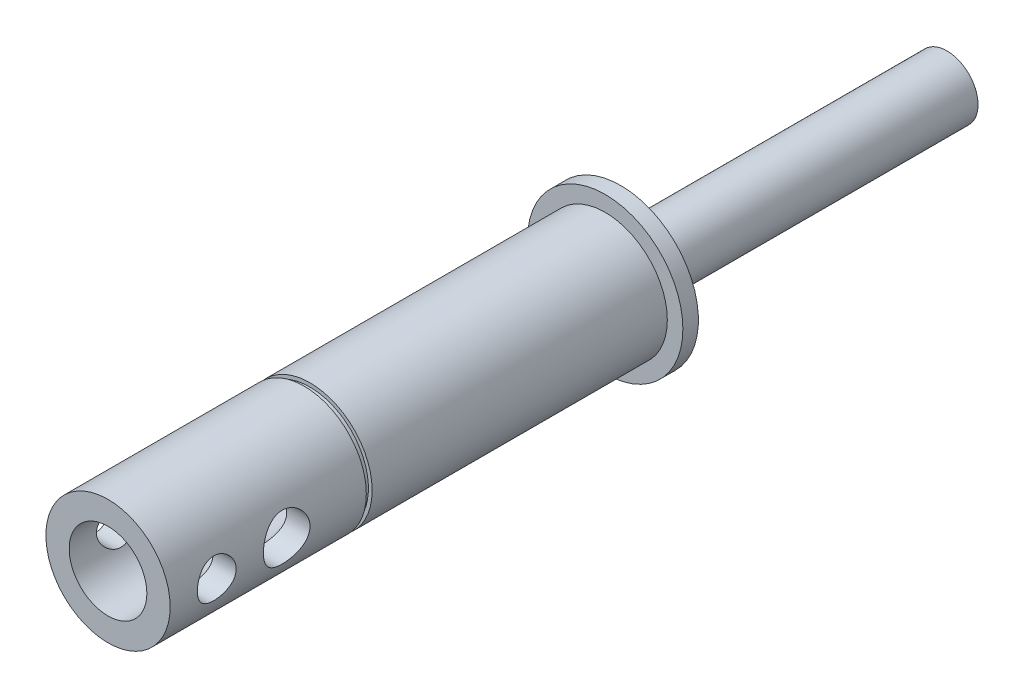
SolidWorks part; units mm, degrees
other "Markup1"
sketch "Sketch20" plane through (-15.875, -15.875, 171.45) normal (-1, 0, 0) x (0, 0, -1)
material "6061 Alloy"
ref_plane "Front Plane" through (0, 0, 0) normal (0, 0, 1) x (1, 0, 0)
ref_plane "Top Plane" through (0, 0, 0) normal (0, 1, 0) x (1, 0, 0)
ref_plane "Right Plane" through (0, 0, 0) normal (1, 0, 0) x (0, 0, -1)
sketch "Sketch1" plane through (0, 0, 0) normal (0, 0, 1) x (1, 0, 0)
  circle A0 centre (0, 0) radius 15.875
  dimension "D1" = 31.75
extrude "RawStock" add sketch "Sketch1" along normal blind 194.6402
sketch "Sketch10" plane through (0, 0, 194.6402) normal (0, 0, 1) x (1, 0, 0)
  circle A0 centre (0, 0) radius 12.7
extrude "FacingOp" cut sketch "Sketch10" against normal blind 23.1902
hole_wizard "ReliefHole" positions "Sketch2" profile "Sketch3" legacy
sketch "Sketch2" plane through (0, 0, 194.6402) normal (0, 0, 1) x (1, 0, 0)
  point P0 (0, 0)
sketch "Sketch3" plane through (0, 0, 194.6402) normal (1, 0, 0) x (0, -1, 0)
  line L0 (0, 0) -> (0, 95.8905)
  line L1 (0, 95.8905) -> (6.35, 92.075)
  line L2 (6.35, 92.075) -> (6.35, 0)
  line L4 (6.35, 0) -> (0, 0)
  line L6 (0, 95.8905) -> (-6.35, 92.075) construction
  line L7 (0, -4.2442) -> (0, 117.3081) construction
  dimension "Diameter" = 12.7
  dimension "Depth" = 92.075
  dimension "Drill Angle" = 118
hole_wizard "WiresHole" positions "Sketch4" profile "Sketch5" legacy
sketch "Sketch4" plane through (0, 0, 194.6402) normal (0, 0, 1) x (1, 0, 0)
  point P0 (0, 0)
sketch "Sketch5" plane through (0, 0, 194.6402) normal (1, 0, 0) x (0, -1, 0)
  line L0 (0, 0) -> (0, 120.0345)
  line L1 (0, 120.0345) -> (7.9375, 115.2652)
  line L2 (7.9375, 115.2652) -> (7.9375, 0)
  line L4 (7.9375, 0) -> (0, 0)
  line L6 (0, 120.0345) -> (-7.9375, 115.2652) construction
  line L7 (0, -4.2442) -> (0, 117.3081) construction
  dimension "Diameter" = 15.875
  dimension "Depth" = 115.2652
  dimension "Drill Angle" = 118
sketch "Sketch6" plane through (0, 0, 194.6402) normal (0, 0, 1) x (1, 0, 0)
  circle A0 centre (0, 0) radius 12.7
  dimension "D1" = 25.4
extrude "ShaftDiam" cut sketch "Sketch6" against normal blind 124.7902 flip side to cut
ref_plane "GroovePlane" through (0, 0, 130.175) normal (0, 0, 1) x (1, 0, 0)
sketch "Sketch7" plane through (0, 0, 130.175) normal (0, 0, 1) x (1, 0, 0)
  circle A0 centre (0, 0) radius 11.938
  dimension "D1" = 23.876
extrude "Groove" cut sketch "Sketch7" along normal blind 1.1906 flip side to cut
sketch "Sketch8" plane through (0, 0, 0) normal (0, 0, -1) x (-1, 0, 0)
  circle A0 centre (0, 0) radius 6.35
  dimension "D1" = 12.7
extrude "EncoderShaft" cut sketch "Sketch8" against normal blind 66.675 flip side to cut
sketch "Sketch9" plane through (0, 0, 0) normal (0, 0, -1) x (-1, 0, 0)
  circle A0 centre (0, 0) radius 6.35
  dimension "D1" = 12.7
ref_plane "Plane2" through (-12.7, 0, 0) normal (-1, 0, 0) x (0, 1, 0)
sketch "Sketch12" plane through (-12.7, 0, 0) normal (-1, 0, 0) x (0, 1, 0)
  line L0 (-12.7, -171.45) -> (12.7, -171.45) construction
  line L1 (0, -194.6402) -> (0, -74.6057) construction
  line L2 (-7.9375, -171.45) -> (7.9375, -171.45) construction
  circle A0 centre (0, -161.925) radius 3.9687
  circle A1 centre (0, -147.6375) radius 4.7625
  dimension "D1" = 7.9375
  dimension "D3" = 9.525
  dimension "D2" = 9.525
  dimension "D4" = 23.8125
extrude "Holes_Top" cut sketch "Sketch12" against normal through all
sketch "Sketch13" plane through (-12.7, 0, 0) normal (-1, 0, 0) x (0, 1, 0)
  circle A0 centre (0, -147.6375) radius 4.7625 construction
  point P0 (0, -142.875)
ref_plane "Plane1" through (0, -11.938, 0) normal (0, -1, 0) x (-1, 0, 0)
sketch "GrooveSketch" plane through (0, -11.938, 0) normal (0, -1, 0) x (-1, 0, 0)
  line L0 (0, -131.3656) -> (0, -130.175)
  line L1 (12.7, -131.3656) -> (-12.7, -131.3656) construction
  line L2 (0, -194.6402) -> (0, -74.6057) construction
  line L3 (-13.97, -130.175) -> (13.97, -130.175) construction
hole_wizard "SlipRingHole" positions "Sketch18" profile "Sketch19" legacy
sketch "Sketch18" plane through (0, 0, 66.675) normal (0, 0, -1) x (-1, 0, 0)
  line L0 (0, 17.4625) -> (0, -17.4625) construction
  circle A0 centre (0, 0) radius 8.7312 construction
  point P0 (0, -8.7312)
  dimension "D1" = 17.4625
sketch "Sketch19" plane through (0, -8.7312, 66.675) normal (1, 0, 0) x (0, 1, 0)
  line L0 (0, 0) -> (0, 26.8308)
  line L1 (0, 26.8308) -> (2.3812, 25.4)
  line L2 (2.3812, 25.4) -> (2.3812, 0)
  line L4 (2.3812, 0) -> (0, 0)
  line L6 (0, 26.8308) -> (-2.3812, 25.4) construction
  line L7 (0, -4.2442) -> (0, 117.3081) construction
  dimension "Diameter" = 4.7625
  dimension "Depth" = 25.4
  dimension "Drill Angle" = 118
sketch "Sketch23" plane through (-12.7, 0, 0) normal (-1, 0, 0) x (0, 1, 0)
  point P0 (0, -161.925)
  point P1 (0, -147.6375)
